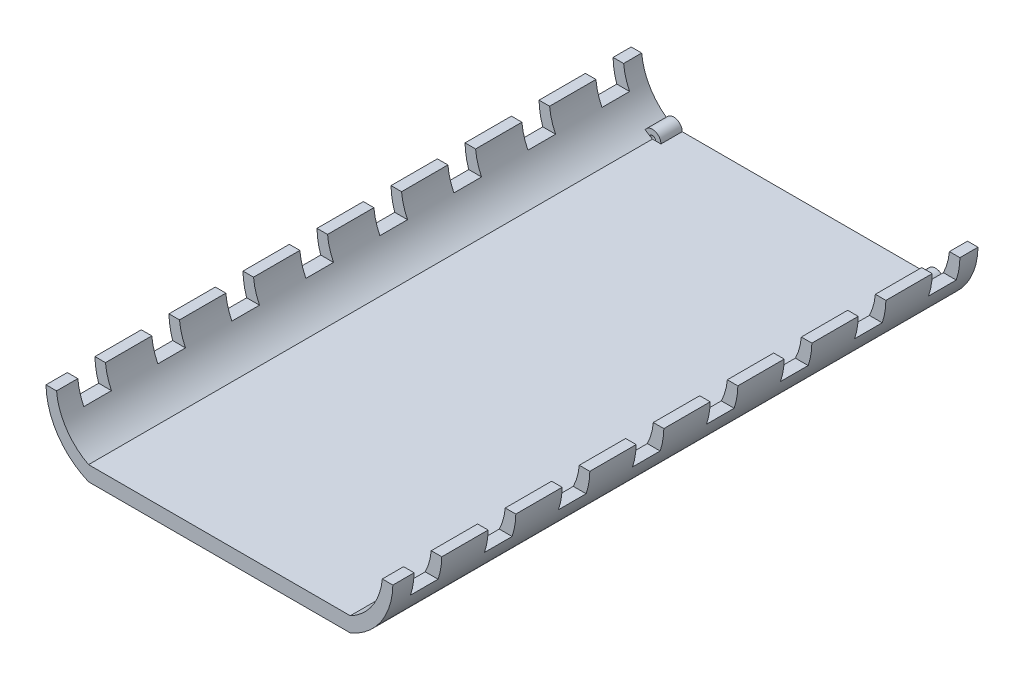
SolidWorks part; units mm, degrees
ref_plane "Front Plane" through (0, 0, 0) normal (0, 0, 1) x (1, 0, 0)
ref_plane "Top Plane" through (0, 0, 0) normal (0, 1, 0) x (1, 0, 0)
ref_plane "Right Plane" through (0, 0, 0) normal (1, 0, 0) x (0, 0, -1)
sketch "Sketch1" plane through (0, 0, 0) normal (0, 1, 0) x (1, 0, 0)
  line L1 (61.5, -137.5) -> (-61.5, -137.5)
  line L2 (61.5, -137.5) -> (61.5, 137.5)
  line L3 (61.5, 137.5) -> (-61.5, 137.5)
  line L4 (-61.5, -137.5) -> (-61.5, 137.5)
  line L5 (61.5, -137.5) -> (-61.5, 137.5) construction
  line L6 (61.5, 137.5) -> (-61.5, -137.5) construction
  point P0 (0, 0)
  dimension "D1" = 123
  dimension "D2" = 275
extrude "Boss-Extrude1" add sketch "Sketch1" along normal blind 7
sketch "Sketch2" plane through (0, 0, 137.5) normal (0, 0, 1) x (1, 0, 0)
  line L0 (-61.5, 7) -> (-76.548, 22.0465) construction
  line L1 (0, 0) -> (0, 29.496) construction
  line L2 (-61.5, 0) -> (-81.498, 19.996) construction
  line L3 (-81.498, 19.996) -> (-81.498, 29.496) construction
  line L4 (-81.498, 29.496) -> (-76.548, 29.496)
  line L5 (-76.548, 29.496) -> (-76.548, 22.0465) construction
  line L6 (-61.5, 0) -> (61.5, 0) construction
  line L7 (-61.5, 7) -> (-61.5, 0)
  line L8 (81.498, 29.496) -> (76.548, 29.496)
  line L9 (61.5, 7) -> (61.5, 0)
  arc A0 (-81.498, 29.496) -> (-61.5, 0) centre (-49.0031, 30) ccw
  arc A1 (-76.548, 29.496) -> (-61.5, 7) centre (-48.4655, 32) ccw
  arc A2 (81.498, 29.496) -> (61.5, 0) centre (49.0031, 30) cw
  arc A3 (76.548, 29.496) -> (61.5, 7) centre (48.4655, 32) cw
  dimension "D1" = 21.28
  dimension "D2" = 4.95
  dimension "D3" = 28.28
  dimension "D4" = 9.5
  dimension "D5" = 30
  dimension "D6" = 32
extrude "Boss-Extrude2" add sketch "Sketch2" against normal up to surface (275 mm away) contours A1 L7 A0 L4 | L8 A3 L9 A2 up to face at (0, 3.5, -137.5)
sketch "Sketch3" plane through (0, 0, 0) normal (1, 0, 0) x (0, 0, -1)
  line L0 (137.5, 29.496) -> (-137.5, 29.496) construction
  line L1 (-127.5, 29.496) -> (-114.5, 29.496)
  line L2 (-127.5, 29.496) -> (-127.5, 19.496)
  line L3 (-127.5, 19.496) -> (-114.5, 19.496)
  line L8 (-92.7143, 29.496) -> (-92.7143, 19.496)
  line L9 (-92.7143, 29.496) -> (-79.7143, 29.496)
  line L10 (-79.7143, 29.496) -> (-79.7143, 19.496)
  line L11 (-92.7143, 19.496) -> (-79.7143, 19.496)
  line L12 (-57.9286, 29.496) -> (-57.9286, 19.496)
  line L13 (-57.9286, 29.496) -> (-44.9286, 29.496)
  line L14 (-44.9286, 29.496) -> (-44.9286, 19.496)
  line L15 (-57.9286, 19.496) -> (-44.9286, 19.496)
  line L16 (-23.1429, 29.496) -> (-23.1429, 19.496)
  line L17 (-23.1429, 29.496) -> (-10.1429, 29.496)
  line L18 (-10.1429, 29.496) -> (-10.1429, 19.496)
  line L19 (-23.1429, 19.496) -> (-10.1429, 19.496)
  line L20 (11.6429, 29.496) -> (11.6429, 19.496)
  line L21 (11.6429, 29.496) -> (24.6429, 29.496)
  line L22 (24.6429, 29.496) -> (24.6429, 19.496)
  line L23 (11.6429, 19.496) -> (24.6429, 19.496)
  line L24 (46.4286, 29.496) -> (46.4286, 19.496)
  line L25 (46.4286, 29.496) -> (59.4286, 29.496)
  line L26 (59.4286, 29.496) -> (59.4286, 19.496)
  line L27 (46.4286, 19.496) -> (59.4286, 19.496)
  line L28 (81.2143, 29.496) -> (81.2143, 19.496)
  line L29 (81.2143, 29.496) -> (94.2143, 29.496)
  line L30 (94.2143, 29.496) -> (94.2143, 19.496)
  line L31 (81.2143, 19.496) -> (94.2143, 19.496)
  line L32 (116, 29.496) -> (116, 19.496)
  line L33 (116, 29.496) -> (129, 29.496)
  line L35 (116, 19.496) -> (129, 19.496)
  line L37 (137.5, 29.496) -> (-137.5, 29.496) construction
  line L38 (-127.5, 38.996) -> (-127.5, 29.496) construction
  line L39 (-114.5, 29.496) -> (-114.5, 19.496)
  line L40 (-114.5, 38.996) -> (-114.5, 29.496) construction
  line L41 (129, 29.496) -> (129, 19.496)
  line L42 (129, 38.996) -> (129, 29.496) construction
  dimension "D1" = 10
  dimension "D2" = 8
extrude "Cut-Extrude1" cut sketch "Sketch3" against normal through all both and the other way through all contours L2 L1 L39 L3 | L8 L11 L10 L9 | L12 L15 L14 L13 | L16 L19 L18 L17 | L20 L23 L22 L21 | L24 L27 L26 L25 | L28 L31 L30 L29 | L32 L35 L41 L33
sketch "Sketch4" plane through (0, 0, -137.5) normal (0, 0, -1) x (-1, 0, 0)
  line L0 (0, 0) -> (0, 7) construction
  line L1 (-61.5, 7) -> (61.5, 7) construction
  circle A0 centre (61.5, 7) radius 1.5
  circle A1 centre (61.5, 7) radius 4
  circle A2 centre (-61.5, 7) radius 4
  circle A3 centre (-61.5, 7) radius 1.5
  dimension "D1" = 3
  dimension "D2" = 8
extrude "Boss-Extrude3" add sketch "Sketch4" against normal blind 10
sketch "Sketch5" plane through (0, 0, -137.5) normal (0, 0, -1) x (-1, 0, 0)
  circle A0 centre (61.5, 7) radius 1.5
  circle A1 centre (-61.5, 7) radius 1.5
  dimension "D1" = 3
  dimension "D2" = 3
extrude "Cut-Extrude2" cut sketch "Sketch5" against normal blind 10
sketch "Sketch8" plane through (0, 0, 0) normal (0, -1, 0) x (1, 0, 0)
  line L0 (-0.0256, 57.4884) -> (-0.0256, -44.5116) construction
  line L1 (-50.0256, -29.5701) -> (49.9744, -29.5701) construction
  arc A0 (-50.0256, -29.5701) -> (-0.0256, 57.4884) centre (39.7518, -23.2442) cw
  arc A1 (-0.0256, 38.2605) -> (-32.6817, -19.623) centre (42.2063, -23.719) ccw
  arc A2 (-0.0256, 38.2605) -> (32.6306, -19.623) centre (-42.2575, -23.719) cw
  arc A3 (49.9744, -29.5701) -> (-0.0256, 57.4884) centre (-39.803, -23.2442) ccw
  arc A4 (-50.0256, -29.5701) -> (49.9744, -29.5701) centre (-0.0256, 45.263) ccw
  arc A5 (-32.6817, -19.623) -> (32.6306, -19.623) centre (-0.0256, 47.763) ccw
  dimension "D3" = 90
  dimension "D4" = 75
  dimension "D9" = 90
  dimension "D1" = 100
  dimension "D2" = 102
  dimension "D5" = 2.5
  dimension "D6" = 87.0586
  dimension "D7" = 57.8835
  dimension "D8" = 82.7721
  dimension "D10" = 2.5
extrude "Cut-Extrude3" cut sketch "Sketch8" against normal blind 3 contours A0 A3 A4 | A1 A5 A2
sketch "Sketch9" plane through (0, 0, 0) normal (0, -1, 0) x (1, 0, 0)
  line L0 (-50.0889, -28.6883) -> (38.178, 22.4605) construction
  line L1 (11.8277, 51.2634) -> (5.8441, 51.7067)
  line L2 (-0.0889, 58.3703) -> (-0.0889, -43.8551) construction
  line L3 (-49.9678, -14.9758) -> (-47.3599, -20.3794)
  line L4 (-44.0439, -15.9285) -> (-49.9678, -14.9758)
  line L5 (-44.0439, -15.9285) -> (-45.6972, -18.1477) construction
  line L6 (-47.3599, -20.3794) -> (-48.837, -22.3621) construction
  line L7 (-47.3599, -20.3794) -> (-50.3006, -19.7443)
  line L8 (-45.4283, -18.6228) -> (-42.7418, -23.3693)
  line L9 (-42.7418, -23.3693) -> (-39.7214, -18.6859) construction
  line L10 (-39.7214, -18.6859) -> (-45.1135, -18.2003)
  line L11 (-49.905, -24.6318) -> (-48.5689, -22.8383)
  line L12 (-42.7418, -23.3693) -> (-43.8348, -25.0642) construction
  line L13 (-45.6931, -27.9456) -> (-48.5689, -22.8383)
  line L14 (-48.2824, -22.4538) -> (-42.7418, -23.3693)
  line L15 (-48.5689, -22.8383) -> (-48.837, -22.3621) construction
  line L16 (-48.837, -22.3621) -> (-50.3056, -24.3333) construction
  line L17 (-48.837, -22.3621) -> (-48.2824, -22.4538) construction
  line L18 (-48.2824, -22.4538) -> (-45.4283, -18.6228)
  line L19 (-48.5689, -22.8383) -> (-48.2824, -22.4538) construction
  line L20 (-45.6972, -18.1477) -> (-47.3599, -20.3794) construction
  line L21 (-45.1135, -18.2003) -> (-45.6972, -18.1477) construction
  line L22 (-45.6972, -18.1477) -> (-45.4283, -18.6228) construction
  line L23 (-45.1135, -18.2003) -> (-43.6305, -16.2097)
  line L24 (-45.4283, -18.6228) -> (-45.1135, -18.2003) construction
  line L25 (-39.2905, -18.9395) -> (-40.7869, -21.2598)
  line L26 (-43.8348, -25.0642) -> (-45.6931, -27.9456) construction
  line L27 (-50.3056, -24.3333) -> (-49.905, -24.6318)
  line L28 (-35.4051, -21.3791) -> (-40.7869, -21.2598)
  line L29 (-41.4061, -21.2461) -> (-41.389, -21.2717)
  line L30 (-36.1561, -23.7758) -> (-34.9595, -21.6011)
  line L31 (-30.7483, -23.5189) -> (-36.1561, -23.7758)
  line L32 (-36.4101, -24.2375) -> (-33.0992, -28.5716)
  line L33 (-30.2812, -23.6993) -> (-31.4515, -26.2144)
  line L34 (-38.713, -28.423) -> (-33.0992, -28.5716)
  line L35 (-38.713, -28.423) -> (-36.4101, -24.2375)
  line L36 (-38.0831, -26.2419) -> (-43.725, -25.8157)
  line L37 (-43.8692, -26.0393) -> (-40.4599, -30.5618)
  line L38 (-40.4599, -30.5618) -> (-40.0223, -30.8026)
  line L39 (-40.0223, -30.8026) -> (-38.9442, -28.8432)
  line L40 (-35.3964, -33.5088) -> (-38.9442, -28.8432)
  line L41 (-2.0353, 58.2366) -> (11.9562, -43.0268) construction
  line L42 (-26.1016, -25.5957) -> (-31.4515, -26.2144)
  line L43 (-31.6852, -26.7168) -> (-28.0912, -30.7796)
  line L44 (-26.5199, -28.0729) -> (-25.6322, -25.7548)
  line L45 (-21.1981, -27.0783) -> (-26.5199, -28.0729)
  line L46 (-26.7083, -28.565) -> (-22.8354, -32.4051)
  line L47 (-20.7105, -27.1924) -> (-21.5257, -29.8447)
  line L48 (-28.4166, -33.0263) -> (-22.8354, -32.4051)
  line L49 (-28.4166, -33.0263) -> (-26.7083, -28.565)
  line L50 (-28.0912, -30.7796) -> (-33.7384, -31.1296)
  line L51 (-33.8501, -31.3698) -> (-29.8544, -35.3841)
  line L52 (-29.8544, -35.3841) -> (-29.3879, -35.5627)
  line L53 (-29.3879, -35.5627) -> (-28.5881, -33.4742)
  line L54 (-24.4352, -37.6103) -> (-28.5881, -33.4742)
  line L55 (-3.945, 57.8378) -> (23.7745, -40.5577) construction
  line L56 (-16.3086, -28.4989) -> (-21.5257, -29.8447)
  line L57 (-21.6885, -30.3743) -> (-17.5723, -33.9069)
  line L58 (-16.3862, -31.0107) -> (-15.8242, -28.5929)
  line L59 (-11.2507, -29.297) -> (-16.3862, -31.0107)
  line L60 (-16.5055, -31.5239) -> (-12.1434, -34.7978)
  line L61 (-10.752, -29.3429) -> (-11.1966, -32.0822)
  line L62 (-17.5872, -36.1771) -> (-12.1434, -34.7978)
  line L63 (-17.5872, -36.1771) -> (-16.5055, -31.5239)
  line L64 (-17.5723, -33.9069) -> (-23.1184, -35.0265)
  line L65 (-23.196, -35.2791) -> (-18.6887, -38.7094)
  line L66 (-18.6887, -38.7094) -> (-18.2021, -38.8225)
  line L67 (-18.2021, -38.8225) -> (-17.6957, -36.6442)
  line L68 (-13.0157, -40.173) -> (-17.6957, -36.6442)
  line L69 (-5.7815, 57.1796) -> (32.331, -30.0564) construction
  line L70 (-6.2106, -30.0342) -> (-11.1966, -32.0822)
  line L71 (-11.2853, -32.6291) -> (-6.7243, -35.5651)
  line L72 (-5.9458, -32.5338) -> (-5.72, -30.0619)
  line L73 (-1.0931, -30.1334) -> (-5.9458, -32.5338)
  line L74 (-5.9937, -33.0586) -> (-1.2246, -35.7046)
  line L75 (-0.5929, -30.1105) -> (-0.6583, -32.885)
  line L76 (-6.4283, -37.816) -> (-1.2246, -35.7046)
  line L77 (-6.4283, -37.816) -> (-5.9937, -33.0586)
  line L78 (-6.7243, -35.5651) -> (-12.065, -37.4333)
  line L79 (-12.1073, -37.6937) -> (-7.1729, -40.4753)
  line L80 (-7.1729, -40.4753) -> (-6.6754, -40.5207)
  line L81 (-6.6754, -40.5207) -> (-6.472, -38.2935)
  line L82 (-1.353, -41.1486) -> (-6.472, -38.2935)
  line L83 (10.3335, -40.5187) -> (10.8273, -40.4403)
  line L84 (4.0023, -30.1727) -> (-0.6583, -32.885)
  line L85 (-0.6714, -33.4389) -> (4.2485, -35.723)
  line L86 (4.6048, -32.6136) -> (4.4902, -30.1341)
  line L87 (9.0833, -29.5716) -> (4.6048, -32.6136)
  line L88 (4.6292, -33.14) -> (9.7156, -35.1084)
  line L89 (9.5757, -29.4807) -> (9.8906, -32.2378)
  line L90 (4.8498, -37.9121) -> (9.7156, -35.1084)
  line L91 (4.8498, -37.9121) -> (4.6292, -33.14)
  line L92 (4.2485, -35.723) -> (-0.7862, -38.3046)
  line L93 (-0.7924, -38.5682) -> (4.4762, -40.6483)
  line L94 (4.4762, -40.6483) -> (4.9752, -40.6252)
  line L95 (4.9752, -40.6252) -> (4.8719, -38.3912)
  line L96 (10.3335, -40.5187) -> (4.8719, -38.3912)
  line L97 (-1.353, -41.1486) -> (-0.8531, -41.1382)
  line L98 (14.1377, -28.912) -> (9.8906, -32.2378)
  line L99 (9.9535, -32.7883) -> (15.1397, -34.3776)
  line L100 (15.0671, -31.2487) -> (14.6142, -28.8082)
  line L101 (19.087, -27.6224) -> (15.0671, -31.2487)
  line L102 (15.1632, -31.7668) -> (20.4712, -33.0205)
  line L103 (19.5625, -27.4655) -> (20.2517, -30.153)
  line L104 (16.0349, -36.4638) -> (20.4712, -33.0205)
  line L105 (16.0349, -36.4638) -> (15.1632, -31.7668)
  line L106 (15.1397, -34.3776) -> (10.5057, -37.6239)
  line L107 (10.5356, -37.8861) -> (16.0394, -39.2254)
  line L108 (16.0394, -39.2254) -> (16.5305, -39.1342)
  line L109 (16.5305, -39.1342) -> (16.1224, -36.9353)
  line L110 (21.8238, -38.2953) -> (16.1224, -36.9353)
  line L111 (-13.0157, -40.173) -> (-12.5191, -40.2312)
  line L112 (24.0048, -26.2759) -> (20.2517, -30.153)
  line L113 (20.3893, -30.6897) -> (25.7442, -31.5541)
  line L114 (25.2441, -28.4646) -> (24.4614, -26.1091)
  line L115 (28.7298, -24.3222) -> (25.2441, -28.4646)
  line L116 (25.4102, -28.9647) -> (30.8398, -29.4801)
  line L117 (29.1797, -24.1026) -> (30.2299, -26.6696)
  line L118 (26.9166, -33.4982) -> (30.8398, -29.4801)
  line L119 (26.9166, -33.4982) -> (25.4102, -28.9647)
  line L120 (25.7442, -31.5541) -> (21.5982, -35.4042)
  line L121 (21.6639, -35.6604) -> (27.2989, -36.2332)
  line L122 (27.2989, -36.2332) -> (27.773, -36.0756)
  line L123 (27.773, -36.0756) -> (27.0678, -33.9533)
  line L124 (31.7808, -34.4113) -> (27.0678, -33.9533)
  line L125 (-24.4352, -37.6103) -> (-23.9513, -37.7364)
  line L126 (32.6776, -23.3255) -> (30.2299, -26.6696)
  line L127 (30.4397, -27.1824) -> (32.5504, -27.2305)
  line L128 (-35.3964, -33.5088) -> (-34.9346, -33.7006)
  line L129 (21.8238, -38.2953) -> (22.3024, -38.1506)
  line L130 (28.7298, -24.3222) -> (29.1797, -24.1026)
  line L131 (24.0048, -26.2759) -> (24.4614, -26.1091)
  line L132 (19.087, -27.6224) -> (19.5625, -27.4655)
  line L133 (14.1377, -28.912) -> (14.6142, -28.8082)
  line L134 (9.0833, -29.5716) -> (9.5757, -29.4807)
  line L135 (4.0023, -30.1727) -> (4.4902, -30.1341)
  line L136 (-1.0931, -30.1334) -> (-0.5929, -30.1105)
  line L137 (-6.2106, -30.0342) -> (-5.72, -30.0619)
  line L138 (-11.2507, -29.297) -> (-10.752, -29.3429)
  line L139 (-16.3086, -28.4989) -> (-15.8242, -28.5929)
  line L140 (-21.1981, -27.0783) -> (-20.7105, -27.1924)
  line L141 (-26.1016, -25.5957) -> (-25.6322, -25.7548)
  line L142 (-30.7483, -23.5189) -> (-30.2812, -23.6993)
  line L143 (-35.4051, -21.3791) -> (-34.9595, -21.6011)
  line L144 (8.0407, 46.6095) -> (11.8277, 51.2634)
  line L145 (5.8441, 51.7067) -> (7.8645, 53.9359)
  line L146 (6.3995, 49.1556) -> (0.9457, 49.2022)
  line L147 (3.4915, 44.2448) -> (6.6081, 48.6717)
  line L148 (3.434, 56.037) -> (4.3191, 53.9832)
  line L149 (-1.5418, 54.0463) -> (4.3191, 53.9832)
  line L150 (4.5089, 53.5428) -> (0.9457, 49.2022)
  line L151 (4.5089, 53.5428) -> (6.3995, 49.1556)
  line L152 (6.6081, 48.6717) -> (7.5905, 46.3921)
  line L153 (3.0564, 43.9984) -> (1.7951, 46.4545)
  line L154 (3.8928, 56.2347) -> (3.434, 56.037)
  line L155 (-0.999, 41.8534) -> (1.7951, 46.4545)
  line L156 (2.1166, 46.9839) -> (2.0859, 46.9819)
  line L157 (-2.6992, 43.7021) -> (-1.4141, 41.5785)
  line L158 (-5.1806, 38.8904) -> (-2.6992, 43.7021)
  line L159 (-2.972, 44.1529) -> (-8.3809, 43.4526)
  line L160 (-5.5704, 38.5761) -> (-7.1634, 40.8471)
  line L161 (-5.4453, 48.24) -> (-8.3809, 43.4526)
  line L162 (-5.4453, 48.24) -> (-2.972, 44.1529)
  line L163 (-3.8714, 46.604) -> (-0.6813, 51.2769)
  line L164 (-0.8028, 51.5136) -> (-6.4241, 50.8223)
  line L165 (-6.4241, 50.8223) -> (-6.8515, 50.5637)
  line L166 (-6.8515, 50.5637) -> (-5.6936, 48.6503)
  line L167 (-11.508, 47.9106) -> (-5.6936, 48.6503)
  line L168 (-9.3025, 35.9046) -> (-7.1634, 40.8471)
  line L169 (-7.4816, 41.3007) -> (-12.797, 40.2196)
  line L170 (-11.2387, 37.5054) -> (-9.675, 35.5777)
  line L171 (-13.0382, 32.3994) -> (-11.2387, 37.5054)
  line L172 (-11.5706, 37.9147) -> (-16.8328, 36.4807)
  line L173 (-13.3808, 32.0341) -> (-15.2701, 34.0663)
  line L174 (-14.5801, 41.6248) -> (-16.8328, 36.4807)
  line L175 (-14.5801, 41.6248) -> (-11.5706, 37.9147)
  line L176 (-12.797, 40.2196) -> (-10.2766, 45.2852)
  line L177 (-10.4287, 45.5021) -> (-15.9031, 44.0488)
  line L178 (-43.8692, -26.0393) -> (-45.2625, -28.1997)
  line L179 (-43.725, -25.8157) -> (-43.8692, -26.0393) construction
  line L180 (-43.725, -25.8157) -> (-44.0566, -25.7907) construction
  line L181 (-44.0566, -25.7907) -> (-43.8692, -26.0393) construction
  line L182 (-41.373, -21.2469) -> (-41.4061, -21.2461)
  line L183 (-40.7869, -21.2598) -> (-41.373, -21.2469) construction
  line L184 (-41.0872, -21.7255) -> (-43.725, -25.8157)
  line L185 (-40.7869, -21.2598) -> (-41.0872, -21.7255) construction
  line L186 (-41.0872, -21.7255) -> (-38.0831, -26.2419)
  line L187 (-41.389, -21.2717) -> (-41.0872, -21.7255) construction
  line L188 (-31.4515, -26.2144) -> (-32.0667, -26.2856) construction
  line L189 (-32.0667, -26.2856) -> (-31.6852, -26.7168) construction
  line L190 (-31.6852, -26.7168) -> (-33.7384, -31.1296)
  line L191 (-31.4515, -26.2144) -> (-31.6852, -26.7168) construction
  line L192 (-34.0688, -31.15) -> (-33.8501, -31.3698) construction
  line L193 (-33.7384, -31.1296) -> (-34.0688, -31.15) construction
  line L194 (-33.8501, -31.3698) -> (-34.9346, -33.7006)
  line L195 (-33.7384, -31.1296) -> (-33.8501, -31.3698) construction
  line L196 (-23.442, -35.0919) -> (-23.196, -35.2791) construction
  line L197 (-23.196, -35.2791) -> (-23.9513, -37.7364)
  line L198 (-23.1184, -35.0265) -> (-23.196, -35.2791) construction
  line L199 (-23.1184, -35.0265) -> (-23.442, -35.0919) construction
  line L200 (-22.1254, -29.9993) -> (-21.6885, -30.3743) construction
  line L201 (-21.5257, -29.8447) -> (-22.1254, -29.9993) construction
  line L202 (-21.6885, -30.3743) -> (-23.1184, -35.0265)
  line L203 (-21.5257, -29.8447) -> (-21.6885, -30.3743) construction
  line L204 (-12.3761, -37.5421) -> (-12.1073, -37.6937) construction
  line L205 (-12.1073, -37.6937) -> (-12.5191, -40.2312)
  line L206 (-12.065, -37.4333) -> (-12.1073, -37.6937) construction
  line L207 (-12.065, -37.4333) -> (-12.3761, -37.5421) construction
  line L208 (-0.0899, 44.1495) -> (0.1587, 48.5959) construction
  line L209 (-11.7694, -32.3175) -> (-11.2853, -32.6291) construction
  line L210 (-11.1966, -32.0822) -> (-11.7694, -32.3175) construction
  line L211 (-11.2853, -32.6291) -> (-12.065, -37.4333)
  line L212 (-11.1966, -32.0822) -> (-11.2853, -32.6291) construction
  line L213 (-0.6583, -32.885) -> (-1.1936, -33.1965) construction
  line L214 (-1.1936, -33.1965) -> (-0.6714, -33.4389) construction
  line L215 (-0.6714, -33.4389) -> (-0.7862, -38.3046)
  line L216 (-0.6583, -32.885) -> (-0.6714, -33.4389) construction
  line L217 (-0.7862, -38.3046) -> (-1.0794, -38.4549) construction
  line L218 (-1.0794, -38.4549) -> (-0.7924, -38.5682) construction
  line L219 (-0.7924, -38.5682) -> (-0.8531, -41.1382)
  line L220 (-0.7862, -38.3046) -> (-0.7924, -38.5682) construction
  line L221 (9.8906, -32.2378) -> (9.403, -32.6196) construction
  line L222 (9.9535, -32.7883) -> (10.5057, -37.6239)
  line L223 (9.8906, -32.2378) -> (9.9535, -32.7883) construction
  line L224 (9.403, -32.6196) -> (9.9535, -32.7883) construction
  line L225 (10.5057, -37.6239) -> (10.2356, -37.8131) construction
  line L226 (10.2356, -37.8131) -> (10.5356, -37.8861) construction
  line L227 (10.5356, -37.8861) -> (10.8273, -40.4403)
  line L228 (10.5057, -37.6239) -> (10.5356, -37.8861) construction
  line L229 (21.356, -35.6291) -> (21.6639, -35.6604) construction
  line L230 (21.5982, -35.4042) -> (21.356, -35.6291) construction
  line L231 (21.6639, -35.6604) -> (22.3024, -38.1506)
  line L232 (21.5982, -35.4042) -> (21.6639, -35.6604) construction
  line L233 (20.2517, -30.153) -> (19.8209, -30.5979) construction
  line L234 (19.8209, -30.5979) -> (20.3893, -30.6897) construction
  line L235 (20.3893, -30.6897) -> (21.5982, -35.4042)
  line L236 (20.2517, -30.153) -> (20.3893, -30.6897) construction
  line L237 (30.2299, -26.6696) -> (29.8641, -27.1693) construction
  line L238 (30.4397, -27.1824) -> (32.1836, -31.4455)
  line L239 (30.2299, -26.6696) -> (30.4397, -27.1824) construction
  line L240 (29.8641, -27.1693) -> (30.4397, -27.1824) construction
  line L241 (-15.9031, 44.0488) -> (-16.291, 43.7341)
  line L242 (-16.291, 43.7341) -> (-14.8822, 41.9972)
  line L243 (-20.5406, 40.4687) -> (-14.8822, 41.9972)
  line L244 (-16.7133, 28.8752) -> (-15.2701, 34.0663)
  line L245 (-15.6474, 34.4721) -> (-20.7649, 32.6736)
  line L246 (-18.8497, 30.1983) -> (-17.0369, 28.5027)
  line L247 (-19.9334, 24.894) -> (-18.8497, 30.1983)
  line L248 (-19.2345, 30.5582) -> (-24.2509, 28.4175)
  line L249 (-20.2224, 24.485) -> (-22.3725, 26.2397)
  line L250 (-22.7235, 33.8216) -> (-24.2509, 28.4175)
  line L251 (-22.7235, 33.8216) -> (-19.2345, 30.5582)
  line L252 (-20.7649, 32.6736) -> (-18.9614, 38.0365)
  line L253 (-19.1413, 38.23) -> (-24.3658, 36.0417)
  line L254 (-24.3658, 36.0417) -> (-24.707, 35.6769)
  line L255 (-24.707, 35.6769) -> (-23.0737, 34.1491)
  line L256 (-28.4697, 31.8605) -> (-23.0737, 34.1491)
  line L257 (-23.0918, 20.8977) -> (-22.3725, 26.2397)
  line L258 (-22.8018, 26.59) -> (-27.6249, 24.1081)
  line L259 (-25.389, 21.9182) -> (-23.3612, 20.4867)
  line L260 (-25.7365, 16.5155) -> (-25.389, 21.9182)
  line L261 (-25.8195, 22.2221) -> (-30.4956, 19.4149)
  line L262 (-25.9668, 16.0708) -> (-28.3368, 17.5147)
  line L263 (-29.7222, 24.9772) -> (-30.4956, 19.4149)
  line L264 (-29.7222, 24.9772) -> (-25.8195, 22.2221)
  line L265 (-27.6249, 24.1081) -> (-26.5725, 29.6674)
  line L266 (-26.7768, 29.8341) -> (-31.6529, 26.9516)
  line L267 (-31.6529, 26.9516) -> (-31.941, 26.5435)
  line L268 (-31.941, 26.5435) -> (-30.114, 25.2538)
  line L269 (-35.146, 22.2481) -> (-30.114, 25.2538)
  line L270 (-40.4437, 11.8124) -> (-40.6228, 11.3455)
  line L271 (-28.3182, 12.1224) -> (-28.3368, 17.5147)
  line L272 (-28.81, 17.803) -> (-33.2481, 14.6843)
  line L273 (-30.7334, 12.821) -> (-28.5288, 11.6805)
  line L274 (-30.3382, 7.4216) -> (-30.7334, 12.821)
  line L275 (-31.2015, 13.0631) -> (-35.4494, 9.6424)
  line L276 (-30.5057, 6.9497) -> (-33.0508, 8.0555)
  line L277 (-35.4445, 15.2581) -> (-35.4494, 9.6424)
  line L278 (-35.4445, 15.2581) -> (-31.2015, 13.0631)
  line L279 (-33.2481, 14.6843) -> (-32.9664, 20.3353)
  line L280 (-33.1916, 20.4724) -> (-37.6273, 16.9498)
  line L281 (-37.6273, 16.9498) -> (-37.8569, 16.5061)
  line L282 (-37.8569, 16.5061) -> (-35.8705, 15.4785)
  line L283 (-40.4437, 11.8124) -> (-35.8705, 15.4785)
  line L284 (-35.146, 22.2481) -> (-35.387, 21.81)
  line L285 (-32.2941, 2.7145) -> (-33.0508, 8.0555)
  line L286 (-33.559, 8.2763) -> (-37.5285, 4.5795)
  line L287 (-34.7825, 3.078) -> (-32.4425, 2.2499)
  line L288 (-33.6519, -2.2166) -> (-34.7825, 3.078)
  line L289 (-35.2792, 3.2537) -> (-39.019, -0.7162)
  line L290 (-33.7538, -2.7068) -> (-36.4258, -1.9599)
  line L291 (-39.7828, 4.8473) -> (-39.019, -0.7162)
  line L292 (-39.7828, 4.8473) -> (-35.2792, 3.2537)
  line L293 (-37.5285, 4.5795) -> (-38.0229, 10.2159)
  line L294 (-38.2649, 10.321) -> (-42.1766, 6.2243)
  line L295 (-42.1766, 6.2243) -> (-42.3432, 5.7534)
  line L296 (-42.3432, 5.7534) -> (-40.2349, 5.0073)
  line L297 (-44.2634, 0.7498) -> (-40.2349, 5.0073)
  line L298 (-28.4697, 31.8605) -> (-28.7685, 31.4596)
  line L299 (-34.9447, -7.1487) -> (-36.4258, -1.9599)
  line L300 (-36.9594, -1.8107) -> (-40.3856, -6.016)
  line L301 (-37.4599, -7.1276) -> (-35.0286, -7.6275)
  line L302 (-35.6154, -12.2176) -> (-37.4599, -7.1276)
  line L303 (-37.976, -7.0215) -> (-41.1372, -11.4659)
  line L304 (-35.6501, -12.717) -> (-38.3983, -12.3429)
  line L305 (-42.6554, -6.0592) -> (-41.1372, -11.4659)
  line L306 (-42.6554, -6.0592) -> (-37.976, -7.0215)
  line L307 (-40.3856, -6.016) -> (-41.6468, -0.5004)
  line L308 (-41.9015, -0.4292) -> (-45.2151, -5.0229)
  line L309 (-45.2151, -5.0229) -> (-45.3157, -5.5122)
  line L310 (-45.3157, -5.5122) -> (-43.1251, -5.9627)
  line L311 (-45.8782, -9.8152) -> (-43.1251, -5.9627)
  line L312 (-20.5406, 40.4687) -> (-20.8918, 40.1127)
  line L313 (-36.726, -16.1348) -> (-38.3983, -12.3429)
  line L314 (-38.9473, -12.2682) -> (-40.0443, -14.0722)
  line L315 (-11.508, 47.9106) -> (-11.905, 47.6067)
  line L316 (-44.2634, 0.7498) -> (-44.3774, 0.263)
  line L317 (-35.6154, -12.2176) -> (-35.6501, -12.717)
  line L318 (-34.9447, -7.1487) -> (-35.0286, -7.6275)
  line L319 (-33.6519, -2.2166) -> (-33.7538, -2.7068)
  line L320 (-32.2941, 2.7145) -> (-32.4425, 2.2499)
  line L321 (-30.3382, 7.4216) -> (-30.5057, 6.9497)
  line L322 (-28.3182, 12.1224) -> (-28.5288, 11.6805)
  line L323 (-25.7365, 16.5155) -> (-25.9668, 16.0708)
  line L324 (-23.0918, 20.8977) -> (-23.3612, 20.4867)
  line L325 (-19.9334, 24.894) -> (-20.2224, 24.485)
  line L326 (-16.7133, 28.8752) -> (-17.0369, 28.5027)
  line L327 (-13.0382, 32.3994) -> (-13.3808, 32.0341)
  line L328 (-9.3025, 35.9046) -> (-9.675, 35.5777)
  line L329 (-5.1806, 38.8904) -> (-5.5704, 38.5761)
  line L330 (-0.999, 41.8534) -> (-1.4141, 41.5785)
  line L331 (-0.8028, 51.5136) -> (-1.9772, 53.8004)
  line L332 (2.0994, 46.9556) -> (2.1166, 46.9839)
  line L333 (1.542, 46.9474) -> (-0.6813, 51.2769)
  line L334 (1.542, 46.9474) -> (-3.8714, 46.604)
  line L335 (-7.4816, 41.3007) -> (-10.2766, 45.2852)
  line L336 (-10.4287, 45.5021) -> (-11.905, 47.6067)
  line L337 (-19.1413, 38.23) -> (-20.8918, 40.1127)
  line L338 (-15.6474, 34.4721) -> (-18.9614, 38.0365)
  line L339 (-26.7768, 29.8341) -> (-28.7685, 31.4596)
  line L340 (-22.8018, 26.59) -> (-26.5725, 29.6674)
  line L341 (-28.81, 17.803) -> (-32.9664, 20.3353)
  line L342 (-33.1916, 20.4724) -> (-35.387, 21.81)
  line L343 (-33.559, 8.2763) -> (-38.0229, 10.2159)
  line L344 (-38.2649, 10.321) -> (-40.6228, 11.3455)
  line L345 (-41.9015, -0.4292) -> (-44.3774, 0.263)
  line L346 (-36.9594, -1.8107) -> (-41.6468, -0.5004)
  line L347 (-38.9473, -12.2682) -> (-43.5111, -11.647)
  line L348 (8.0407, 46.6095) -> (6.9455, 49.1509) construction
  line L349 (5.8441, 51.7067) -> (4.8656, 53.9773) construction
  line L350 (0.9457, 49.2022) -> (3.4915, 44.2448) construction
  line L351 (0.9457, 49.2022) -> (0.0244, 50.9962) construction
  line L352 (4.3191, 53.9832) -> (4.8656, 53.9773) construction
  line L353 (4.8656, 53.9773) -> (3.8928, 56.2347) construction
  line L354 (4.8656, 53.9773) -> (4.5089, 53.5428) construction
  line L355 (4.3191, 53.9832) -> (4.5089, 53.5428) construction
  line L356 (6.9455, 49.1509) -> (5.8441, 51.7067) construction
  line L357 (6.6081, 48.6717) -> (6.9455, 49.1509) construction
  line L358 (6.9455, 49.1509) -> (6.3995, 49.1556) construction
  line L359 (6.3995, 49.1556) -> (6.6081, 48.6717) construction
  line L360 (0.0244, 50.9962) -> (-1.5418, 54.0463) construction
  line L361 (-0.6813, 51.2769) -> (-0.8028, 51.5136) construction
  line L362 (-0.6813, 51.2769) -> (-0.4938, 51.5516) construction
  line L363 (-0.4938, 51.5516) -> (-0.8028, 51.5136) construction
  line L364 (1.7951, 46.4545) -> (2.0994, 46.9556) construction
  line L365 (1.7951, 46.4545) -> (1.542, 46.9474) construction
  line L366 (2.0859, 46.9819) -> (1.542, 46.9474) construction
  line L367 (-7.1634, 40.8471) -> (-6.9174, 41.4154) construction
  line L368 (-6.9174, 41.4154) -> (-7.4816, 41.3007) construction
  line L369 (-7.1634, 40.8471) -> (-7.4816, 41.3007) construction
  line L370 (-10.1291, 45.5816) -> (-10.4287, 45.5021) construction
  line L371 (-10.2766, 45.2852) -> (-10.1291, 45.5816) construction
  line L372 (-10.2766, 45.2852) -> (-10.4287, 45.5021) construction
  line L373 (-18.8562, 38.3494) -> (-19.1413, 38.23) construction
  line L374 (-18.9614, 38.0365) -> (-19.1413, 38.23) construction
  line L375 (-18.9614, 38.0365) -> (-18.8562, 38.3494) construction
  line L376 (-15.1043, 34.6629) -> (-15.6474, 34.4721) construction
  line L377 (-15.2701, 34.0663) -> (-15.1043, 34.6629) construction
  line L378 (-15.2701, 34.0663) -> (-15.6474, 34.4721) construction
  line L379 (-26.5112, 29.9912) -> (-26.7768, 29.8341) construction
  line L380 (-26.5725, 29.6674) -> (-26.7768, 29.8341) construction
  line L381 (-26.5725, 29.6674) -> (-26.5112, 29.9912) construction
  line L382 (-22.2898, 26.8535) -> (-22.8018, 26.59) construction
  line L383 (-22.3725, 26.2397) -> (-22.2898, 26.8535) construction
  line L384 (-22.3725, 26.2397) -> (-22.8018, 26.59) construction
  line L385 (-28.3368, 17.5147) -> (-28.339, 18.134) construction
  line L386 (-28.339, 18.134) -> (-28.81, 17.803) construction
  line L387 (-28.3368, 17.5147) -> (-28.81, 17.803) construction
  line L388 (-32.9664, 20.3353) -> (-32.95, 20.6643) construction
  line L389 (-32.95, 20.6643) -> (-33.1916, 20.4724) construction
  line L390 (-32.9664, 20.3353) -> (-33.1916, 20.4724) construction
  line L391 (-33.0508, 8.0555) -> (-33.1377, 8.6687) construction
  line L392 (-33.0508, 8.0555) -> (-33.559, 8.2763) construction
  line L393 (-33.1377, 8.6687) -> (-33.559, 8.2763) construction
  line L394 (-38.0229, 10.2159) -> (-38.0517, 10.5444) construction
  line L395 (-38.0517, 10.5444) -> (-38.2649, 10.321) construction
  line L396 (-38.0229, 10.2159) -> (-38.2649, 10.321) construction
  line L397 (-41.7204, -0.1782) -> (-41.9015, -0.4292) construction
  line L398 (-41.6468, -0.5004) -> (-41.7204, -0.1782) construction
  line L399 (-41.6468, -0.5004) -> (-41.9015, -0.4292) construction
  line L400 (-36.4258, -1.9599) -> (-36.5958, -1.3644) construction
  line L401 (-36.5958, -1.3644) -> (-36.9594, -1.8107) construction
  line L402 (-36.4258, -1.9599) -> (-36.9594, -1.8107) construction
  line L403 (-38.3983, -12.3429) -> (-38.6482, -11.7763) construction
  line L404 (-38.3983, -12.3429) -> (-38.9473, -12.2682) construction
  line L405 (-38.6482, -11.7763) -> (-38.9473, -12.2682) construction
  line L406 (38.2948, -35.3727) -> (41.6705, -30.4124)
  line L407 (36.1579, -29.7661) -> (38.2948, -35.3727)
  line L408 (41.6705, -30.4124) -> (42.5909, -33.2767)
  line L409 (39.1834, -29.6179) -> (41.9507, -24.918)
  line L410 (36.3847, -24.644) -> (38.6601, -29.5565)
  line L411 (46.6257, -30.4903) -> (44.4045, -30.2299)
  line L412 (47.3896, -25.1858) -> (44.4045, -30.2299)
  line L413 (43.9282, -30.1741) -> (41.9507, -24.918)
  line L414 (43.9282, -30.1741) -> (39.1834, -29.6179)
  line L415 (38.6601, -29.5565) -> (36.1948, -29.2675)
  line L416 (36.3888, -24.144) -> (39.1465, -24.2798)
  line L417 (46.5675, -30.9865) -> (46.6257, -30.4903)
  line L418 (36.5588, -19.5594) -> (39.1465, -24.2798)
  line L419 (39.4442, -24.8228) -> (39.4578, -24.7953)
  line L420 (39.0099, -19.0114) -> (36.5283, -19.0625)
  line L421 (36.0836, -14.4566) -> (39.0099, -19.0114)
  line L422 (39.5368, -19.0005) -> (41.6347, -13.9662)
  line L423 (36.0063, -13.9619) -> (38.7695, -13.7178)
  line L424 (44.313, -18.9021) -> (41.6347, -13.9662)
  line L425 (44.313, -18.9021) -> (39.5368, -19.0005)
  line L426 (42.1092, -19.4472) -> (44.561, -24.5463)
  line L427 (44.8267, -24.5594) -> (47.0387, -19.3456)
  line L428 (47.0387, -19.3456) -> (47.0284, -18.8462)
  line L429 (47.0284, -18.8462) -> (44.7924, -18.8923)
  line L430 (47.0591, -13.487) -> (44.7924, -18.8923)
  line L431 (35.5587, -9.394) -> (38.7695, -13.7178)
  line L432 (39.3215, -13.669) -> (41.0429, -8.5251)
  line L433 (37.9132, -8.5176) -> (35.4619, -8.9079)
  line L434 (34.391, -4.4062) -> (37.9132, -8.5176)
  line L435 (38.4336, -8.4348) -> (39.8228, -3.1606)
  line L436 (34.246, -3.9269) -> (36.9506, -3.3067)
  line L437 (43.1514, -7.6836) -> (39.8228, -3.1606)
  line L438 (43.1514, -7.6836) -> (38.4336, -8.4348)
  line L439 (41.0429, -8.5251) -> (44.1696, -13.2407)
  line L440 (44.4335, -13.2174) -> (45.9122, -7.7498)
  line L441 (45.9122, -7.7498) -> (45.8336, -7.2565)
  line L442 (45.8336, -7.2565) -> (43.625, -7.6082)
  line L443 (45.1305, -1.9435) -> (43.625, -7.6082)
  line L444 (33.1765, 0.5386) -> (36.9506, -3.3067)
  line L445 (37.4906, -3.1829) -> (38.4919, 2.1482)
  line L446 (35.3906, 1.7273) -> (33.0157, 1.0051)
  line L447 (31.3387, 5.3179) -> (35.3906, 1.7273)
  line L448 (35.8947, 1.8806) -> (36.549, 7.2952)
  line L449 (31.1291, 5.7727) -> (33.7237, 6.7574)
  line L450 (40.4653, 3.2704) -> (36.549, 7.2952)
  line L451 (40.4653, 3.2704) -> (35.8947, 1.8806)
  line L452 (38.4919, 2.1482) -> (42.2345, -2.0951)
  line L453 (42.492, -2.036) -> (43.2091, 3.5826)
  line L454 (43.2091, 3.5826) -> (43.0638, 4.0606)
  line L455 (43.0638, 4.0606) -> (40.9241, 3.4099)
  line L456 (41.6401, 9.2273) -> (40.9241, 3.4099)
  line L457 (29.4571, 10.0514) -> (33.7237, 6.7574)
  line L458 (34.2418, 6.954) -> (34.5039, 12.3719)
  line L459 (31.4894, 11.5305) -> (29.2358, 10.4901)
  line L460 (26.9843, 14.5328) -> (31.4894, 11.5305)
  line L461 (31.9679, 11.7514) -> (31.8748, 17.2046)
  line L462 (26.7143, 14.9546) -> (29.1498, 16.2851)
  line L463 (36.3052, 13.7537) -> (31.8748, 17.2046)
  line L464 (36.3052, 13.7537) -> (31.9679, 11.7514)
  line L465 (34.5039, 12.3719) -> (38.7921, 8.6809)
  line L466 (39.0387, 8.7744) -> (38.9805, 14.4385)
  line L467 (38.9805, 14.4385) -> (38.7711, 14.8921)
  line L468 (38.7711, 14.8921) -> (36.7406, 13.9547)
  line L469 (36.6537, 19.8153) -> (36.7406, 13.9547)
  line L470 (30.265, 29.6212) -> (29.9501, 30.0097)
  line L471 (24.4706, 18.9652) -> (29.1498, 16.2851)
  line L472 (29.6361, 16.5508) -> (29.1542, 21.9536)
  line L473 (26.2833, 20.7075) -> (24.1932, 19.3685)
  line L474 (21.4096, 23.065) -> (26.2833, 20.7075)
  line L475 (26.727, 20.9918) -> (25.8885, 26.381)
  line L476 (21.0846, 23.446) -> (23.3149, 25.0972)
  line L477 (30.7494, 23.5689) -> (25.8885, 26.381)
  line L478 (30.7494, 23.5689) -> (26.727, 20.9918)
  line L479 (29.1542, 21.9536) -> (33.9073, 18.8842)
  line L480 (34.1387, 19.0106) -> (33.3058, 24.6135)
  line L481 (33.3058, 24.6135) -> (33.0363, 25.0341)
  line L482 (33.0363, 25.0341) -> (31.1532, 23.8276)
  line L483 (30.265, 29.6212) -> (31.1532, 23.8276)
  line L484 (36.6537, 19.8153) -> (36.3947, 20.2431)
  line L485 (18.3111, 27.1124) -> (23.3149, 25.0972)
  line L486 (23.7602, 25.4269) -> (22.5435, 30.7129)
  line L487 (19.8701, 29.0856) -> (17.983, 27.4731)
  line L488 (14.7196, 30.7538) -> (19.8701, 29.0856)
  line L489 (20.2707, 29.4279) -> (18.7024, 34.6516)
  line L490 (14.346, 31.0872) -> (16.3288, 33.0277)
  line L491 (23.9026, 32.5314) -> (18.7024, 34.6516)
  line L492 (23.9026, 32.5314) -> (20.2707, 29.4279)
  line L493 (22.5435, 30.7129) -> (27.6719, 28.323)
  line L494 (27.884, 28.48) -> (26.2919, 33.916)
  line L495 (26.2919, 33.916) -> (25.9674, 34.2957)
  line L496 (25.9674, 34.2957) -> (24.2671, 32.8429)
  line L497 (22.5943, 38.4604) -> (24.2671, 32.8429)
  line L498 (41.6401, 9.2273) -> (41.4423, 9.6866)
  line L499 (11.0946, 34.3395) -> (16.3288, 33.0277)
  line L500 (16.7248, 33.4153) -> (14.796, 38.485)
  line L501 (12.3705, 36.5071) -> (10.7219, 34.6515)
  line L502 (7.0402, 37.4547) -> (12.3705, 36.5071)
  line L503 (12.7205, 36.901) -> (10.4521, 41.8609)
  line L504 (6.625, 37.7345) -> (8.3231, 39.9274)
  line L505 (15.8934, 40.4723) -> (10.4521, 41.8609)
  line L506 (15.8934, 40.4723) -> (12.7205, 36.901)
  line L507 (14.796, 38.485) -> (20.2033, 36.8194)
  line L508 (20.3923, 37.0044) -> (18.0708, 42.171)
  line L509 (18.0708, 42.171) -> (17.6974, 42.5027)
  line L510 (17.6974, 42.5027) -> (16.212, 40.8308)
  line L511 (14.2521, 45.1414) -> (16.212, 40.8308)
  line L512 (45.1305, -1.9435) -> (44.9978, -1.4614)
  line L513 (4.2031, 40.3752) -> (8.3231, 39.9274)
  line L514 (8.6623, 40.3655) -> (7.6485, 42.2175)
  line L515 (47.0591, -13.487) -> (46.9943, -12.9912)
  line L516 (22.5943, 38.4604) -> (22.2296, 38.8025)
  line L517 (7.0402, 37.4547) -> (6.625, 37.7345)
  line L518 (11.0946, 34.3395) -> (10.7219, 34.6515)
  line L519 (14.7196, 30.7538) -> (14.346, 31.0872)
  line L520 (18.3111, 27.1124) -> (17.983, 27.4731)
  line L521 (21.4096, 23.065) -> (21.0846, 23.446)
  line L522 (24.4706, 18.9652) -> (24.1932, 19.3685)
  line L523 (26.9843, 14.5328) -> (26.7143, 14.9546)
  line L524 (29.4571, 10.0514) -> (29.2358, 10.4901)
  line L525 (31.3387, 5.3179) -> (31.1291, 5.7727)
  line L526 (33.1765, 0.5386) -> (33.0157, 1.0051)
  line L527 (34.391, -4.4062) -> (34.246, -3.9269)
  line L528 (35.5587, -9.394) -> (35.4619, -8.9079)
  line L529 (36.0836, -14.4566) -> (36.0063, -13.9619)
  line L530 (36.5588, -19.5594) -> (36.5283, -19.0625)
  line L531 (44.8267, -24.5594) -> (47.3944, -24.6858)
  line L532 (39.4283, -24.7938) -> (39.4442, -24.8228)
  line L533 (39.6999, -24.307) -> (44.561, -24.5463)
  line L534 (39.6999, -24.307) -> (42.1092, -19.4472)
  line L535 (39.3215, -13.669) -> (44.1696, -13.2407)
  line L536 (44.4335, -13.2174) -> (46.9943, -12.9912)
  line L537 (42.492, -2.036) -> (44.9978, -1.4614)
  line L538 (37.4906, -3.1829) -> (42.2345, -2.0951)
  line L539 (39.0387, 8.7744) -> (41.4423, 9.6866)
  line L540 (34.2418, 6.954) -> (38.7921, 8.6809)
  line L541 (29.6361, 16.5508) -> (33.9073, 18.8842)
  line L542 (34.1387, 19.0106) -> (36.3947, 20.2431)
  line L543 (23.7602, 25.4269) -> (27.6719, 28.323)
  line L544 (27.884, 28.48) -> (29.9501, 30.0097)
  line L545 (20.3923, 37.0044) -> (22.2296, 38.8025)
  line L546 (16.7248, 33.4153) -> (20.2033, 36.8194)
  line L547 (8.6623, 40.3655) -> (11.4822, 44.0073)
  line L548 (36.1579, -29.7661) -> (38.9064, -30.0883) construction
  line L549 (41.6705, -30.4124) -> (44.1261, -30.7003) construction
  line L550 (41.9507, -24.918) -> (36.3847, -24.644) construction
  line L551 (41.9507, -24.918) -> (43.965, -25.0172) construction
  line L552 (44.4045, -30.2299) -> (44.1261, -30.7003) construction
  line L553 (44.1261, -30.7003) -> (46.5675, -30.9865) construction
  line L554 (44.1261, -30.7003) -> (43.9282, -30.1741) construction
  line L555 (44.4045, -30.2299) -> (43.9282, -30.1741) construction
  line L556 (38.9064, -30.0883) -> (41.6705, -30.4124) construction
  line L557 (38.6601, -29.5565) -> (38.9064, -30.0883) construction
  line L558 (38.9064, -30.0883) -> (39.1834, -29.6179) construction
  line L559 (39.1834, -29.6179) -> (38.6601, -29.5565) construction
  line L560 (43.965, -25.0172) -> (47.3896, -25.1858) construction
  line L561 (44.561, -24.5463) -> (44.8267, -24.5594) construction
  line L562 (44.561, -24.5463) -> (44.7051, -24.846) construction
  line L563 (44.7051, -24.846) -> (44.8267, -24.5594) construction
  line L564 (39.1465, -24.2798) -> (39.4283, -24.7938) construction
  line L565 (39.1465, -24.2798) -> (39.6999, -24.307) construction
  line L566 (39.4578, -24.7953) -> (39.6999, -24.307) construction
  line L567 (38.7695, -13.7178) -> (39.1388, -14.215) construction
  line L568 (39.1388, -14.215) -> (39.3215, -13.669) construction
  line L569 (38.7695, -13.7178) -> (39.3215, -13.669) construction
  line L570 (44.3526, -13.5167) -> (44.4335, -13.2174) construction
  line L571 (44.1696, -13.2407) -> (44.3526, -13.5167) construction
  line L572 (44.1696, -13.2407) -> (44.4335, -13.2174) construction
  line L573 (42.4529, -2.3426) -> (42.492, -2.036) construction
  line L574 (42.2345, -2.0951) -> (42.492, -2.036) construction
  line L575 (42.2345, -2.0951) -> (42.4529, -2.3426) construction
  line L576 (37.3843, -3.7487) -> (37.4906, -3.1829) construction
  line L577 (36.9506, -3.3067) -> (37.3843, -3.7487) construction
  line L578 (36.9506, -3.3067) -> (37.4906, -3.1829) construction
  line L579 (39.0419, 8.4659) -> (39.0387, 8.7744) construction
  line L580 (38.7921, 8.6809) -> (39.0387, 8.7744) construction
  line L581 (38.7921, 8.6809) -> (39.0419, 8.4659) construction
  line L582 (34.2139, 6.3789) -> (34.2418, 6.954) construction
  line L583 (33.7237, 6.7574) -> (34.2139, 6.3789) construction
  line L584 (33.7237, 6.7574) -> (34.2418, 6.954) construction
  line L585 (29.1498, 16.2851) -> (29.6872, 15.9773) construction
  line L586 (29.6872, 15.9773) -> (29.6361, 16.5508) construction
  line L587 (29.1498, 16.2851) -> (29.6361, 16.5508) construction
  line L588 (33.9073, 18.8842) -> (34.184, 18.7055) construction
  line L589 (34.184, 18.7055) -> (34.1387, 19.0106) construction
  line L590 (33.9073, 18.8842) -> (34.1387, 19.0106) construction
  line L591 (23.3149, 25.0972) -> (23.8894, 24.8659) construction
  line L592 (23.3149, 25.0972) -> (23.7602, 25.4269) construction
  line L593 (23.8894, 24.8659) -> (23.7602, 25.4269) construction
  line L594 (27.6719, 28.323) -> (27.9708, 28.1837) construction
  line L595 (27.9708, 28.1837) -> (27.884, 28.48) construction
  line L596 (27.6719, 28.323) -> (27.884, 28.48) construction
  line L597 (20.5192, 36.7221) -> (20.3923, 37.0044) construction
  line L598 (20.2033, 36.8194) -> (20.5192, 36.7221) construction
  line L599 (20.2033, 36.8194) -> (20.3923, 37.0044) construction
  line L600 (16.3288, 33.0277) -> (16.9296, 32.8772) construction
  line L601 (16.9296, 32.8772) -> (16.7248, 33.4153) construction
  line L602 (16.3288, 33.0277) -> (16.7248, 33.4153) construction
  line L603 (8.3231, 39.9274) -> (8.9387, 39.8605) construction
  line L604 (8.3231, 39.9274) -> (8.6623, 40.3655) construction
  line L605 (8.9387, 39.8605) -> (8.6623, 40.3655) construction
  line L606 (0.0516, 0.305) -> (4.6858, -22.0983) construction
  line L607 (3.8928, 56.2347) -> (7.8645, 53.9359)
  line L608 (-43.5111, -11.647) -> (-44.7429, -11.4659)
  line L609 (-45.8782, -9.8152) -> (-46.2629, -10.3064)
  line L610 (-40.0443, -14.0722) -> (-40.323, -14.5097)
  line L611 (-36.726, -16.1348) -> (-36.4101, -16.8384)
  line L612 (4.2031, 40.3752) -> (2.0994, 40.5782)
  line L613 (7.6485, 42.2175) -> (7.0086, 43.4243)
  line L614 (11.4822, 44.0073) -> (13.3458, 46.414)
  line L615 (14.2521, 45.1414) -> (13.6743, 46.5497)
  arc A0 (32.5673, -18.7411) -> (-49.1466, -7.9292) centre (-0.0889, 48.6449) cw
  arc A1 (-44.0439, -15.9285) -> (-43.6305, -16.2097) centre (0.1587, 48.5959) ccw
  arc A2 (8.0407, 46.6095) -> (7.5905, 46.3921) centre (41.8191, -23.9333) ccw
  arc A3 (-45.6931, -27.9456) -> (-45.2625, -28.1997) centre (-0.1962, 48.6458) ccw
  arc A4 (-39.7214, -18.6859) -> (-39.2905, -18.9395) centre (0.1587, 48.5959) ccw
  arc A5 (-0.0889, 39.1424) -> (31.0702, -38.2892) centre (-42.3208, -22.8371) cw
  arc A6 (-50.2196, -18.2975) -> (32.4703, -28.4311) centre (-0.2026, 47.3992) ccw construction
  arc A7 (-49.6726, -11.6578) -> (-50.2196, -18.2975) centre (203.7167, -35.8761) ccw
  arc A8 (-50.2196, -18.2975) -> (-50.3056, -24.3333) centre (4.6858, -22.0983) ccw
  circle A9 centre (-0.0889, 0.2857) radius 2.8444
  arc A10 (-1.5418, 54.0463) -> (-1.9772, 53.8004) centre (42.0399, -23.6509) ccw
  arc A11 (3.4915, 44.2448) -> (3.0564, 43.9984) centre (41.8191, -23.9333) ccw
  arc A12 (-0.0889, 39.1424) -> (16.6351, 47.6919) centre (42.143, -22.8371) cw
  arc A13 (9.077, 53.1423) -> (-41.044, -13.4025) centre (40.9634, -23.0221) ccw construction
  arc A14 (36.1579, -29.7661) -> (36.1948, -29.2675) centre (-41.8232, -23.7477) ccw
  arc A15 (47.3896, -25.1858) -> (47.3944, -24.6858) centre (-41.689, -24.08) ccw
  arc A16 (36.3847, -24.644) -> (36.3888, -24.144) centre (-41.8232, -23.7477) ccw
  arc A17 (35.2737, -36.776) -> (41.2973, -33.9299) centre (-70.4473, 194.7747) ccw
  arc A18 (41.2973, -33.9299) -> (46.5675, -30.9865) centre (17.1362, 15.52) ccw
  arc A19 (41.2973, -33.9299) -> (8.7284, 42.7485) centre (-40.6062, -23.4622) ccw construction
  arc M1 (-0.0256, 57.4884) -> (49.9744, -29.5701) centre (-39.803, -23.2442) cw
  arc M3 (-50.0256, -29.5701) -> (-0.0256, 57.4884) centre (39.7518, -23.2442) cw
  dimension "D4" = 78.2129
  dimension "D1" = 1.2509
  dimension "D2" = 1.25
  dimension "D3" = 1.25
  dimension "D5" = 6
  dimension "D6" = 6
  dimension "D7" = 6
  dimension "D8" = 6
  dimension "D9" = 0.5
  dimension "D10" = 0.5
  dimension "D11" = 4.4533
  dimension "D12" = 22.8775
extrude "Boss-Extrude5" add sketch "Sketch9" against normal blind 3 separate body contours A5 L126 L117 L130 L115 L114 L131 L112 L103 L132 L101 L100 L133 L98 L89 L134 L87 L86 L135 L84 L75 L136 L73 L72 L137 L70 L61 L138 L59 L58 L139 L56 L47 L140 L45 L44 L141 L42 L33 L142 L31 L30 L143 L28 L25 A4 L10 L23 A1 L4 M3 | A11 L147 L152 A2 L144 L1 L145 L148 L149 A10 L331 L164 L165 L166 L167 L315 L336 L177 L241 L242 L243 L312 L337 L253 L254 L255 L256 L298 L339 L266 L267 L268 L269 L284 L342 L280 L281 L282 L283 L270 L344 L294 L295 L296 L297 L316 L345 L308 L309 M1 | L408 A18 L417 L411 L412 A15 L531 L427 L428 L429 L430 L515 L536 L440 L441 L442 L443 L512 L537 L453 L454 L455 L456 L498 L539 L466 L467 L468 L469 L484 L542 L480 L481 L482 L483 L470 L544 L494 L495 L496 L497 L516 L545 L508 L509 L510 region at (10.457, 0, 50.2959) region at (13.0971, 0, 45.4902) region at (-47.0945, 0, -16.3186)
sketch "Sketch10" plane through (0, 0, 0) normal (0, -1, 0) x (1, 0, 0)
  line L0 (0, 26.8606) -> (0, 2.3606) construction
  line L1 (25, -23.1394) -> (-25, -23.1394)
  line L2 (25, -23.1394) -> (25, 26.8606)
  line L3 (25, 26.8606) -> (-25, 26.8606)
  line L4 (-25, -23.1394) -> (-25, 26.8606)
  line L5 (25, -23.1394) -> (-25, 26.8606) construction
  line L6 (25, 26.8606) -> (0.3536, 2.2142) construction
  line L7 (-25, 1.8606) -> (25, 1.8606) construction
  line L8 (-25, 1.8606) -> (-4.9497, 6.8104)
  line L9 (-4.9497, 6.8104) -> (0, 26.8606)
  line L10 (0, 24.8606) -> (0, 2.3606)
  line L11 (0, -23.1394) -> (-4.9497, -3.0891)
  line L12 (-4.9497, -3.0891) -> (-25, 1.8606)
  line L13 (0, -23.1394) -> (4.9497, -3.0891)
  line L14 (4.9497, 6.8104) -> (0, 26.8606)
  line L15 (25, 1.8606) -> (4.9497, 6.8104)
  line L16 (4.9497, -3.0891) -> (25, 1.8606)
  line L17 (-4.2426, 6.1033) -> (-0.3536, 2.2142)
  line L18 (0.3536, 1.5071) -> (4.2426, -2.382)
  line L19 (4.2426, 6.1033) -> (0.3536, 2.2142)
  line L20 (-4.2426, -2.382) -> (-0.3536, 1.5071)
  line L21 (0, 24.8606) -> (4.2426, 6.1033)
  line L22 (-23, 1.8606) -> (-0.5, 1.8606)
  line L23 (23, 1.8606) -> (4.2426, -2.382)
  line L24 (0, -21.1394) -> (-4.2426, -2.382)
  line L25 (-23, 1.8606) -> (-4.2426, 6.1033)
  line L26 (0, 1.3606) -> (0, -21.1394)
  line L27 (0.5, 1.8606) -> (23, 1.8606)
  line L28 (0, 1.8606) -> (-25, -23.1394) construction
  line L29 (0, 1.8606) -> (0, -23.1394) construction
  arc A0 (-0.3536, 2.2142) -> (-0.5, 1.8606) centre (0, 1.8606) ccw
  arc A1 (0.3536, 2.2142) -> (0, 2.3606) centre (0, 1.8606) ccw
  arc A2 (0.3536, 1.5071) -> (0.5, 1.8606) centre (0, 1.8606) ccw
  arc A3 (-0.3536, 1.5071) -> (0, 1.3606) centre (0, 1.8606) ccw
  point P0 (0, 1.8606)
  dimension "D12" = 1
  dimension "D1" = 50
  dimension "D2" = 50
  dimension "D3" = 7
  dimension "D4" = 2
  dimension "D5" = 1
  dimension "D6" = 2
  dimension "D7" = 1
  dimension "D8" = 1
  dimension "D9" = 2
  dimension "D10" = 1
  dimension "D11" = 2
extrude "Cut-Extrude4" cut sketch "Sketch10" against normal blind 3 contours L13 L16 L15 L14 L9 L8 L12 L11 L17 A0 L22 L25 L19 A1 L10 L21 L18 A2 L27 L23 L20 A3 L26 L24 region at (0, 0, 1.8606)
